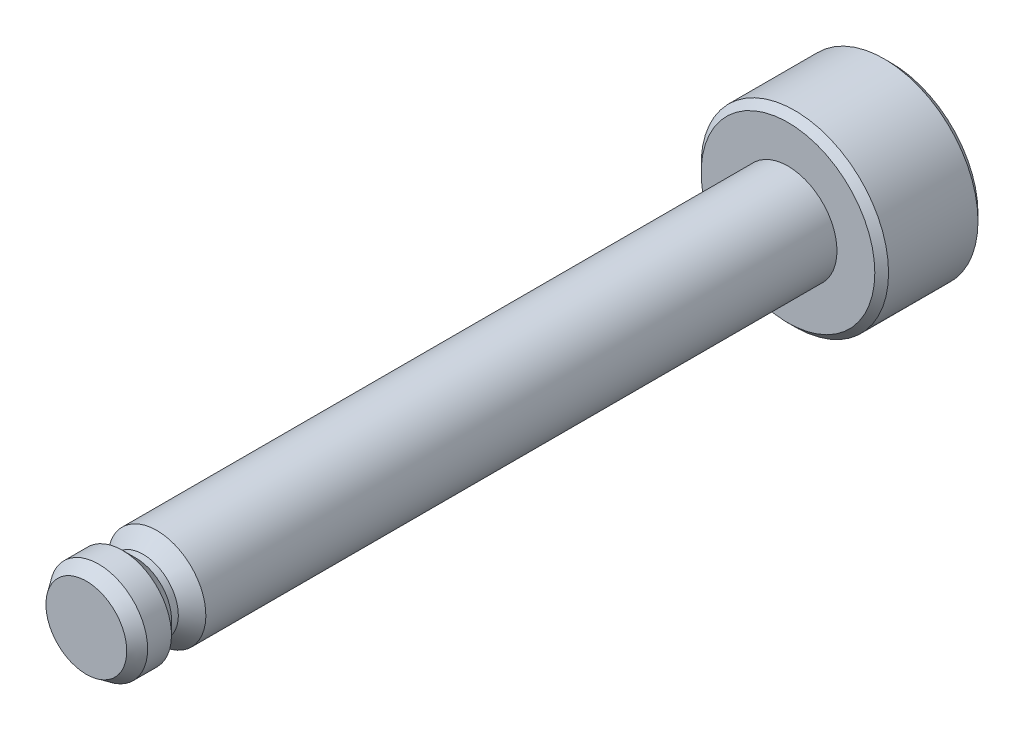
SolidWorks part; units mm, degrees
ref_plane "Front" through (0, 0, 0) normal (0, 0, 1) x (1, 0, 0)
ref_plane "Top" through (0, 0, 0) normal (0, 1, 0) x (1, 0, 0)
ref_plane "Right" through (0, 0, 0) normal (1, 0, 0) x (0, 0, -1)
sketch "Sketch2" plane through (0, 0, 0) normal (0, 0, 1) x (1, 0, 0)
  circle A0 centre (0, 0) radius 1.425
  dimension "D1" = 2.85
extrude "Shaft" add sketch "Sketch2" along normal blind 20.4
sketch "Sketch5" plane through (0, 0, 0) normal (0, 0, 1) x (1, 0, 0)
  circle A0 centre (0, 0) radius 2.725
  dimension "D1" = 5.45
extrude "Head" add sketch "Sketch5" against normal blind 3
sketch "Sketch4" plane through (0, 0, 0) normal (1, 0, 0) x (0, 0, -1)
  line L0 (0, 0) -> (-18.85, 0) construction
  line L1 (-18.85, 0) -> (-18.85, 4.3666) construction
  line L2 (-19.35, 1.425) -> (-18.35, 1.425)
  line L3 (0, 1.425) -> (-20.4, 1.425) construction
  line L6 (-18.35, 1.425) -> (-18.75, 1.025)
  line L7 (-18.75, 1.025) -> (-18.95, 1.025)
  line L8 (-18.95, 1.025) -> (-19.35, 1.425)
  line L10 (-18.85, 50) -> (-18.85, -50) construction
  dimension "D2" = 1
  dimension "D3" = 45
  dimension "D4" = 0.4
revolve "e-Clip Notch Short" cut sketch "Sketch4" angle 360 about L0
chamfer "Chamfer1" distance 0.25 angle 55 1 edges at (1.425, 0, 20.4) first distance on face at (1.425, 0, 20.4)
chamfer "Deburs" distance 0.2 angle 45 2 edges at (2.725, 0, 0) (2.725, 0, -3)
sketch "Sketch6" [suppressed] plane through (0, 0, 0) normal (1, 0, 0) x (0, 0, -1)
  line L0 (0, 0) -> (-27.9, 0) construction
  line L1 (-27.9, 0) -> (-27.9, 1.025) construction
  line L2 (0, 1.425) -> (-29.643, 1.425) construction
  line L3 (-28.4, 1.425) -> (-27.4, 1.425)
  line L4 (-27.4, 1.425) -> (-27.8, 1.025)
  line L5 (-27.8, 1.025) -> (-28, 1.025)
  line L6 (-28, 1.025) -> (-28.4, 1.425)
  line L7 (-27.9, 1.025) -> (-27.9, 1.425) construction
  line L8 (-19.35, 1.425) -> (-18.35, 1.425) construction
  line L9 (-18.95, 1.025) -> (-19.35, 1.425) construction
  line L10 (-27.9, 50) -> (-27.9, -50) construction
revolve "e-Clip Notch Long" [suppressed] cut sketch "Sketch6" angle 360 about L0
equation "\"D1@Sketch2\"=\"Plastic Hardware OD@Box Assy.Assembly\""
equation "\"D1@Sketch5\"=\"Hardware Head Countersink Diameter@Box Assy.Assembly\"-.3mm"
equation "\"D1@Head\"=\"Countersink Depth@Box Assy.Assembly\""
